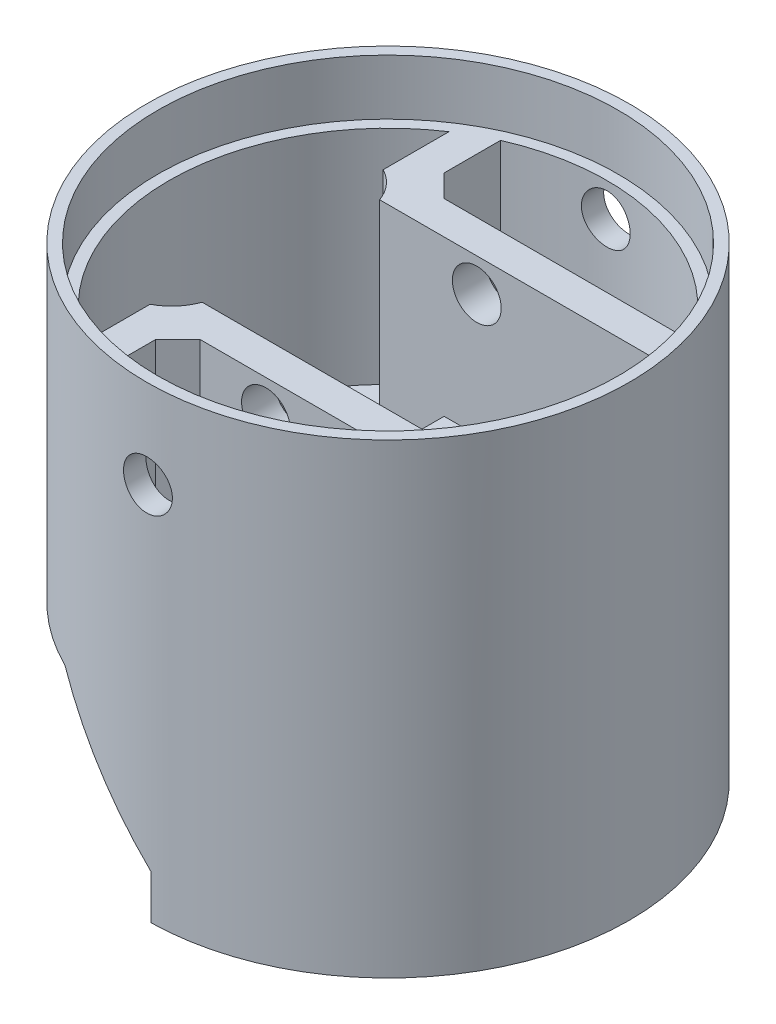
SolidWorks part; units mm, degrees
material "ABS"
ref_plane "Front Plane" through (0, 0, 0) normal (0, 0, 1) x (1, 0, 0)
ref_plane "Top Plane" through (0, 0, 0) normal (0, 1, 0) x (1, 0, 0)
ref_plane "Right Plane" through (0, 0, 0) normal (1, 0, 0) x (0, 0, -1)
sketch "Sketch1" plane through (0, 0, 0) normal (0, 1, 0) x (1, 0, 0)
  line L1 (0, 0) -> (0.4821, 27.6183) construction
  line L2 (0.4821, 27.6183) -> (0.4821, -27.6183)
  line L3 (0.4821, 27.6183) -> (0.4821, -27.6183)
  line L4 (0, 0) -> (27.6225, 0) construction
  circle A0 centre (0, 0) radius 27.6225 construction
  arc A3 (0.4821, -27.6183) -> (0.4821, 27.6183) centre (0, 0) ccw
  arc A4 (0.4821, -27.6183) -> (0.4821, 27.6183) centre (0, 0) ccw
  circle A5 centre (13.1821, 15.24) radius 2.54
  circle A6 centre (13.1821, -15.24) radius 2.54
  arc A8 (4.2522, 22.5903) -> (7.921, 21.5792) centre (0, 0) cw construction
  arc A9 (8.2711, 22.5329) -> (4.4401, 23.5888) centre (0, 0) ccw
  arc A10 (7.5709, 20.6254) -> (4.0642, 21.5918) centre (0, 0) ccw
  arc A11 (7.5709, 20.6254) -> (8.2711, 22.5329) centre (7.921, 21.5792) ccw
  arc A12 (4.4401, 23.5888) -> (4.0642, 21.5918) centre (4.2522, 22.5903) ccw
  circle A13 centre (13.1821, -15.24) radius 2.54 construction
  circle A14 centre (13.1821, 15.24) radius 2.54 construction
  point P4 (6.1075, 22.1608)
  dimension "D1" = 55.245
  dimension "D2" = 0
  dimension "D3" = 89
extrude "base" add sketch "Sketch1" along normal blind 3.81
sketch "Sketch2" plane through (0, 3.81, 0) normal (0, 1, 0) x (1, 0, 0)
  line L1 (0.4821, -25.0783) -> (0.4821, -27.6183)
  line L5 (0.4821, 27.6183) -> (0.4821, -27.6183) construction
  line L7 (0, 0) -> (27.6225, 0) construction
  line L9 (0.4821, 27.6183) -> (0.4821, 25.0783)
  line L10 (24.8812, -3.175) -> (15.9912, -3.175)
  line L19 (15.9912, -3.175) -> (15.9912, 3.175)
  line L20 (15.9912, 3.175) -> (24.8812, 3.175)
  arc A4 (0.4821, -27.6183) -> (0.4821, 27.6183) centre (0, 0) ccw
  arc A5 (0.4821, 25.0783) -> (0.4821, -25.0783) centre (0, 0) cw
  arc A7 (0.4821, -27.6183) -> (0.4821, 27.6183) centre (0, 0) ccw construction
  point P6 (15.9912, 0)
  dimension "D1" = 2.54
  dimension "D2" = 6.35
  dimension "D3" = 8.89
extrude "wall" add sketch "Sketch2" along normal blind 13.97 contours L19 L7 A5 L20 | L7 L19 L10 A5
sketch "Sketch3" plane through (0, 17.78, 0) normal (0, 1, 0) x (1, 0, 0)
  line L1 (0.4821, 25.0783) -> (0.4821, -25.0783) construction
  line L2 (-16.51, -8.255) -> (-16.51, 8.255) construction
  line L3 (-22.225, -8.255) -> (-22.225, 8.255)
  line L4 (-10.795, -8.255) -> (-10.795, 8.255)
  line L5 (-16.51, 0) -> (0, 0) construction
  circle A2 centre (6.8321, 17.4583) radius 3.175
  circle A3 centre (0, 0) radius 27.6225
  arc A4 (0.4821, -27.6183) -> (0.4821, 27.6183) centre (0, 0) ccw construction
  arc A5 (-22.225, -8.255) -> (-10.795, -8.255) centre (-16.51, -8.255) ccw
  arc A6 (-10.795, 8.255) -> (-22.225, 8.255) centre (-16.51, 8.255) ccw
  circle A7 centre (6.8321, -17.4583) radius 3.175
  point P9 (-16.51, 0)
  dimension "D1" = 16.51
  dimension "D4" = 6.35
  dimension "D6" = 6.35
  dimension "D7" = 6.35
  dimension "D2" = 11.43
  dimension "D3" = 16.51
  dimension "D5" = 10.16
  dimension "D8" = 6.35
  dimension "D9" = 10.16
extrude "upper_plate" add sketch "Sketch3" along normal blind 3.81
chamfer "underside_chamfer" distance 2.54 angle 45 2 edges at (16.756, 17.78, 18.6652) (16.756, 17.78, -18.6652)
chamfer "breakaway_chamfer" distance 12.7 angle 45 2 edges at (0.4821, 17.78, -25.078) (0.4821, 17.78, 25.078)
sketch "Sketch4" plane through (0, 21.59, 0) normal (0, 1, 0) x (1, 0, 0)
  line L0 (0, 0) -> (25.0825, 0) construction
  line L1 (22.9326, -10.16) -> (-13.8974, -10.16)
  line L2 (22.9326, -10.16) -> (22.9326, 10.16)
  line L3 (22.9326, 10.16) -> (-13.8974, 10.16)
  line L4 (-13.8974, -10.16) -> (-13.8974, 10.16) construction
  line L5 (-13.8974, 10.16) -> (-13.8974, 20.8805)
  line L6 (-13.8974, -10.16) -> (-13.8974, -20.8805)
  line L7 (-10.0874, -22.9647) -> (-10.0874, -13.97)
  line L8 (-10.0874, -13.97) -> (20.832, -13.97)
  line L9 (-10.0874, 22.9647) -> (-10.0874, 13.97)
  line L10 (-10.0874, 13.97) -> (20.832, 13.97)
  circle A2 centre (0, 0) radius 27.6225
  circle A3 centre (0, 0) radius 27.6225 construction
  arc A4 (22.9326, 10.16) -> (22.9326, -10.16) centre (0, 0) ccw
  point P10 (22.9326, 0)
  dimension "D1" = 2.54
  dimension "D2" = 20.32
  dimension "D3" = 36.83
  dimension "D4" = 3.81
  dimension "D5" = 3.81
  dimension "D6" = 3.81
  dimension "D7" = 3.81
extrude "servo_wall" add sketch "Sketch4" along normal blind 25.4
sketch "Sketch5" plane through (0, 21.59, 0) normal (0, 1, 0) x (1, 0, 0)
  line L0 (22.9326, 10.16) -> (-11.1218, 10.16) construction
  line L1 (-3.7374, 10.16) -> (12.7726, 10.16)
  line L2 (-3.7374, 10.16) -> (-3.7374, -10.16)
  line L3 (-3.7374, -10.16) -> (12.7726, -10.16)
  line L5 (22.9326, -10.16) -> (-11.1218, -10.16) construction
  line L6 (22.9326, -10.16) -> (22.9326, 10.16) construction
  line L7 (12.7726, 10.16) -> (12.7726, -10.16)
  dimension "D1" = 26.67
  dimension "D2" = 16.51
extrude "servo_lower_screwshelf" add sketch "Sketch5" along normal blind 7.62
sketch "Sketch6" plane through (-3.7374, 0, 0) normal (-1, 0, 0) x (0, 0, 1)
  line L0 (-5.08, 25.4) -> (5.08, 25.4) construction
  line L1 (0, 29.21) -> (0, 21.59) construction
  line L2 (-10.16, 29.21) -> (10.16, 29.21) construction
  line L3 (-10.16, 21.59) -> (10.16, 21.59) construction
  point P0 (-5.08, 25.4)
  point P1 (5.08, 25.4)
  point P10 (0, 25.4)
  point P11 (0, 25.4)
  dimension "D1" = 10.16
hole_wizard "#7 (0.201) Diameter Hole1" positions "Sketch6" profile "Sketch7" hole size "#7" standard "ANSI Inch"
sketch "Sketch7" plane through (-3.7374, 25.4, -5.08) normal (0, 1, 0) x (0, 0, 1)
  line L0 (0, 0) -> (0, 16.51)
  line L1 (0, 16.51) -> (2.5527, 16.51)
  line L2 (2.5527, 16.51) -> (2.5527, 0)
  line L5 (2.5527, 0) -> (0, 0)
  line L11 (0, -6.35) -> (0, 107.95) construction
  dimension "Thru Hole Dia." = 5.1054
  dimension "Thru Hole Depth" = 16.51
chamfer "Chamfer3" distance 2.54 angle 45 2 edges at (-10.0874, 34.29, 13.97) (-10.0874, 34.29, -13.97)
sketch "Sketch8" plane through (0, 46.99, 0) normal (0, 1, 0) x (1, 0, 0)
  circle A0 centre (0, 0) radius 26.3525
  circle A1 centre (0, 0) radius 27.6225
  circle A3 centre (0, 0) radius 27.6225 construction
  dimension "D1" = 1.27
extrude "nosecone_ring" add sketch "Sketch8" along normal blind 6.35
ref_plane "nosecone_bolt_plane" through (0, 0, 27.6225) normal (0, 0, 1) x (1, 0, 0)
sketch "Sketch10" plane through (0, 0, 27.6225) normal (0, 0, 1) x (1, 0, 0)
  line L0 (-27.6225, 43.18) -> (27.6225, 43.18) construction
  line L1 (-27.6225, 53.34) -> (-27.6225, 17.78) construction
  line L2 (27.6225, 0) -> (27.6225, 53.34) construction
  line L3 (26.3525, 53.34) -> (-26.3525, 53.34) construction
  circle A0 centre (0, 43.18) radius 2.794
  dimension "D1" = 5.588
  dimension "D2" = 10.16
extrude "Cut-Extrude1" cut sketch "Sketch10" against normal through all
